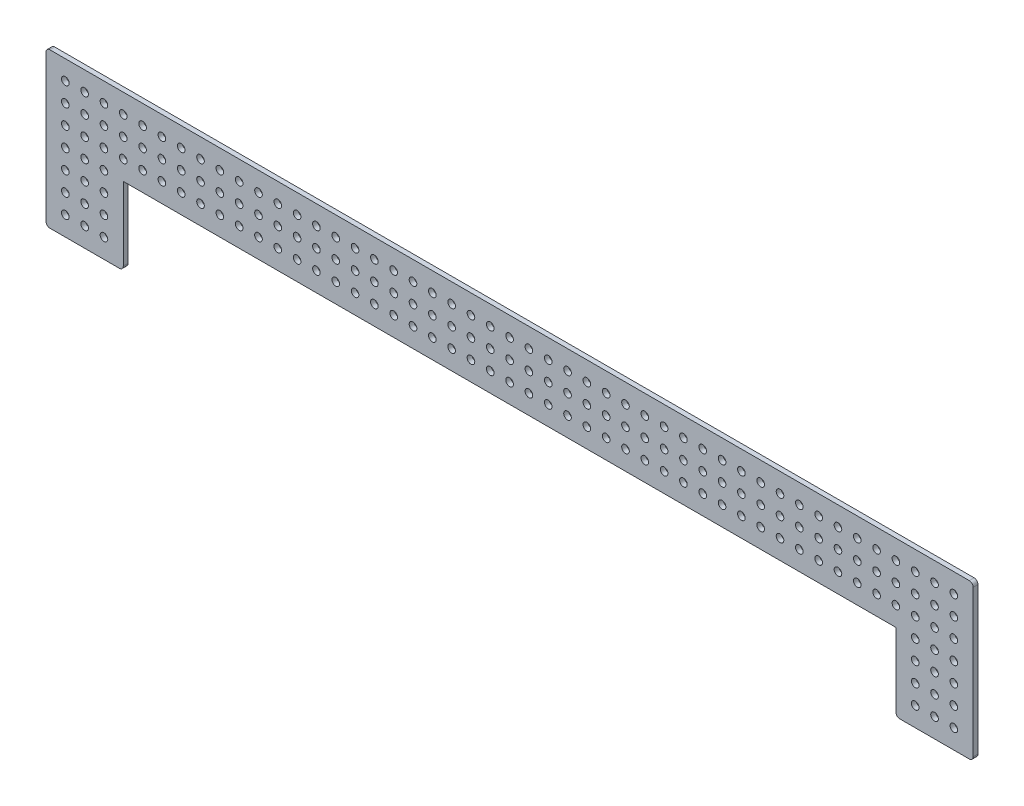
SolidWorks part; units mm, degrees
ref_plane "Front Plane" through (0, 0, 0) normal (0, 0, 1) x (1, 0, 0)
ref_plane "Top Plane" through (0, 0, 0) normal (0, 1, 0) x (1, 0, 0)
ref_plane "Right Plane" through (0, 0, 0) normal (1, 0, 0) x (0, 0, -1)
sketch "Sketch2" plane through (0, 0, 0) normal (0, 0, 1) x (1, 0, 0)
  line L1 (-478.1332, -46.4778) -> (126.3868, -46.4778)
  line L2 (-480.6732, -49.0178) -> (-480.6732, -97.2778)
  line L3 (-480.6732, -97.2778) -> (128.9268, -97.2778)
  line L4 (128.9268, -49.0178) -> (128.9268, -97.2778)
  line L5 (-480.6732, -97.2778) -> (-429.8732, -97.2778)
  line L6 (-480.6732, -97.2778) -> (-480.6732, -145.5378)
  line L7 (-478.1332, -148.0778) -> (-432.4132, -148.0778)
  line L8 (-429.8732, -97.2778) -> (-429.8732, -145.5378)
  line L9 (78.1268, -97.2778) -> (128.9268, -97.2778)
  line L10 (78.1268, -97.2778) -> (78.1268, -145.5378)
  line L11 (80.6668, -148.0778) -> (126.3868, -148.0778)
  line L12 (128.9268, -97.2778) -> (128.9268, -145.5378)
  arc A0 (78.1268, -145.5378) -> (80.6668, -148.0778) centre (80.6668, -145.5378) ccw
  arc A1 (126.3868, -148.0778) -> (128.9268, -145.5378) centre (126.3868, -145.5378) ccw
  arc A2 (126.3868, -46.4778) -> (128.9268, -49.0178) centre (126.3868, -49.0178) cw
  arc A3 (-432.4132, -148.0778) -> (-429.8732, -145.5378) centre (-432.4132, -145.5378) ccw
  arc A4 (-480.6732, -145.5378) -> (-478.1332, -148.0778) centre (-478.1332, -145.5378) ccw
  arc A5 (-478.1332, -46.4778) -> (-480.6732, -49.0178) centre (-478.1332, -49.0178) ccw
  point P12 (0, 0)
  point P13 (0, 0)
  point P16 (78.1268, -148.0778)
  point P19 (128.9268, -148.0778)
  point P22 (128.9268, -46.4778)
  point P25 (-429.8732, -148.0778)
  point P28 (-480.6732, -148.0778)
  dimension "D7" = 2.54
  dimension "D1" = 50.8
  dimension "D2" = 609.6
  dimension "D3" = 50.8
  dimension "D4" = 50.8
  dimension "3" = 50.8
  dimension "D6" = 50.8
extrude "Boss-Extrude1" add sketch "Sketch2" along normal blind 3.175 contours L4 L1 L2 L3 | L8 L3 L6 L7 | L12 L3 L10 L11 region at (-175.8732, -71.88, 0) region at (-455.2732, -122.6511, 0) region at (103.5268, -122.6511, 0)
sketch "Sketch3" plane through (0, 0, 3.175) normal (0, 0, 1) x (1, 0, 0)
  line L0 (-478.1332, -46.4778) -> (126.3868, -46.4778) construction
  line L1 (-480.6732, -49.0178) -> (-480.6732, -145.5378) construction
  line L2 (-478.1332, -148.0778) -> (-432.4132, -148.0778) construction
  line L3 (80.6668, -148.0778) -> (126.3868, -148.0778) construction
  line L4 (78.1268, -97.2778) -> (78.1268, -145.5378) construction
  circle A0 centre (-467.9732, -59.1778) radius 2.505
  circle A1 centre (-455.2732, -59.1778) radius 2.505
  circle A2 centre (-442.5732, -59.1778) radius 2.505
  circle A3 centre (-429.8732, -59.1778) radius 2.505
  circle A4 centre (-417.1732, -59.1778) radius 2.505
  circle A5 centre (-404.4732, -59.1778) radius 2.505
  circle A6 centre (-391.7732, -59.1778) radius 2.505
  circle A7 centre (-379.0732, -59.1778) radius 2.505
  circle A8 centre (-366.3732, -59.1778) radius 2.505
  circle A9 centre (-353.6732, -59.1778) radius 2.505
  circle A10 centre (-340.9732, -59.1778) radius 2.505
  circle A11 centre (-328.2732, -59.1778) radius 2.505
  circle A12 centre (-315.5732, -59.1778) radius 2.505
  circle A13 centre (-302.8732, -59.1778) radius 2.505
  circle A14 centre (-290.1732, -59.1778) radius 2.505
  circle A15 centre (-277.4732, -59.1778) radius 2.505
  circle A16 centre (-264.7732, -59.1778) radius 2.505
  circle A17 centre (-252.0732, -59.1778) radius 2.505
  circle A18 centre (-239.3732, -59.1778) radius 2.505
  circle A19 centre (-226.6732, -59.1778) radius 2.505
  circle A20 centre (-213.9732, -59.1778) radius 2.505
  circle A21 centre (-201.2732, -59.1778) radius 2.505
  circle A22 centre (-188.5732, -59.1778) radius 2.505
  circle A23 centre (-175.8732, -59.1778) radius 2.505
  circle A24 centre (-163.1732, -59.1778) radius 2.505
  circle A25 centre (-150.4732, -59.1778) radius 2.505
  circle A26 centre (-137.7732, -59.1778) radius 2.505
  circle A27 centre (-125.0732, -59.1778) radius 2.505
  circle A28 centre (-112.3732, -59.1778) radius 2.505
  circle A29 centre (-99.6732, -59.1778) radius 2.505
  circle A30 centre (-86.9732, -59.1778) radius 2.505
  circle A31 centre (-74.2732, -59.1778) radius 2.505
  circle A32 centre (-61.5732, -59.1778) radius 2.505
  circle A33 centre (-48.8732, -59.1778) radius 2.505
  circle A34 centre (-36.1732, -59.1778) radius 2.505
  circle A35 centre (-23.4732, -59.1778) radius 2.505
  circle A36 centre (-10.7732, -59.1778) radius 2.505
  circle A37 centre (1.9268, -59.1778) radius 2.505
  circle A38 centre (14.6268, -59.1778) radius 2.505
  circle A39 centre (27.3268, -59.1778) radius 2.505
  circle A40 centre (40.0268, -59.1778) radius 2.505
  circle A41 centre (52.7268, -59.1778) radius 2.505
  circle A42 centre (65.4268, -59.1778) radius 2.505
  circle A43 centre (78.1268, -59.1778) radius 2.505
  circle A44 centre (90.8268, -59.1778) radius 2.505
  circle A45 centre (103.5268, -59.1778) radius 2.505
  circle A46 centre (116.2268, -59.1778) radius 2.505
  circle A47 centre (-455.2732, -71.8778) radius 2.505
  circle A48 centre (-442.5732, -71.8778) radius 2.505
  circle A49 centre (-429.8732, -71.8778) radius 2.505
  circle A50 centre (-417.1732, -71.8778) radius 2.505
  circle A51 centre (-404.4732, -71.8778) radius 2.505
  circle A52 centre (-391.7732, -71.8778) radius 2.505
  circle A53 centre (-379.0732, -71.8778) radius 2.505
  circle A54 centre (-366.3732, -71.8778) radius 2.505
  circle A55 centre (-353.6732, -71.8778) radius 2.505
  circle A56 centre (-340.9732, -71.8778) radius 2.505
  circle A57 centre (-328.2732, -71.8778) radius 2.505
  circle A58 centre (-315.5732, -71.8778) radius 2.505
  circle A59 centre (-302.8732, -71.8778) radius 2.505
  circle A60 centre (-290.1732, -71.8778) radius 2.505
  circle A61 centre (-277.4732, -71.8778) radius 2.505
  circle A62 centre (-264.7732, -71.8778) radius 2.505
  circle A63 centre (-252.0732, -71.8778) radius 2.505
  circle A64 centre (-239.3732, -71.8778) radius 2.505
  circle A65 centre (-226.6732, -71.8778) radius 2.505
  circle A66 centre (-213.9732, -71.8778) radius 2.505
  circle A67 centre (-201.2732, -71.8778) radius 2.505
  circle A68 centre (-188.5732, -71.8778) radius 2.505
  circle A69 centre (-175.8732, -71.8778) radius 2.505
  circle A70 centre (-163.1732, -71.8778) radius 2.505
  circle A71 centre (-150.4732, -71.8778) radius 2.505
  circle A72 centre (-137.7732, -71.8778) radius 2.505
  circle A73 centre (-125.0732, -71.8778) radius 2.505
  circle A74 centre (-112.3732, -71.8778) radius 2.505
  circle A75 centre (-99.6732, -71.8778) radius 2.505
  circle A76 centre (-86.9732, -71.8778) radius 2.505
  circle A77 centre (-74.2732, -71.8778) radius 2.505
  circle A78 centre (-61.5732, -71.8778) radius 2.505
  circle A79 centre (-48.8732, -71.8778) radius 2.505
  circle A80 centre (-36.1732, -71.8778) radius 2.505
  circle A81 centre (-23.4732, -71.8778) radius 2.505
  circle A82 centre (-10.7732, -71.8778) radius 2.505
  circle A83 centre (1.9268, -71.8778) radius 2.505
  circle A84 centre (14.6268, -71.8778) radius 2.505
  circle A85 centre (27.3268, -71.8778) radius 2.505
  circle A86 centre (40.0268, -71.8778) radius 2.505
  circle A87 centre (52.7268, -71.8778) radius 2.505
  circle A88 centre (65.4268, -71.8778) radius 2.505
  circle A89 centre (78.1268, -71.8778) radius 2.505
  circle A90 centre (90.8268, -71.8778) radius 2.505
  circle A91 centre (103.5268, -71.8778) radius 2.505
  circle A92 centre (116.2268, -71.8778) radius 2.505
  circle A93 centre (-455.2732, -84.5778) radius 2.505
  circle A94 centre (-442.5732, -84.5778) radius 2.505
  circle A95 centre (-429.8732, -84.5778) radius 2.505
  circle A96 centre (-417.1732, -84.5778) radius 2.505
  circle A97 centre (-404.4732, -84.5778) radius 2.505
  circle A98 centre (-391.7732, -84.5778) radius 2.505
  circle A99 centre (-379.0732, -84.5778) radius 2.505
  circle A100 centre (-366.3732, -84.5778) radius 2.505
  circle A101 centre (-353.6732, -84.5778) radius 2.505
  circle A102 centre (-340.9732, -84.5778) radius 2.505
  circle A103 centre (-328.2732, -84.5778) radius 2.505
  circle A104 centre (-315.5732, -84.5778) radius 2.505
  circle A105 centre (-302.8732, -84.5778) radius 2.505
  circle A106 centre (-290.1732, -84.5778) radius 2.505
  circle A107 centre (-277.4732, -84.5778) radius 2.505
  circle A108 centre (-264.7732, -84.5778) radius 2.505
  circle A109 centre (-252.0732, -84.5778) radius 2.505
  circle A110 centre (-239.3732, -84.5778) radius 2.505
  circle A111 centre (-226.6732, -84.5778) radius 2.505
  circle A112 centre (-213.9732, -84.5778) radius 2.505
  circle A113 centre (-201.2732, -84.5778) radius 2.505
  circle A114 centre (-188.5732, -84.5778) radius 2.505
  circle A115 centre (-175.8732, -84.5778) radius 2.505
  circle A116 centre (-163.1732, -84.5778) radius 2.505
  circle A117 centre (-150.4732, -84.5778) radius 2.505
  circle A118 centre (-137.7732, -84.5778) radius 2.505
  circle A119 centre (-125.0732, -84.5778) radius 2.505
  circle A120 centre (-112.3732, -84.5778) radius 2.505
  circle A121 centre (-99.6732, -84.5778) radius 2.505
  circle A122 centre (-86.9732, -84.5778) radius 2.505
  circle A123 centre (-74.2732, -84.5778) radius 2.505
  circle A124 centre (-61.5732, -84.5778) radius 2.505
  circle A125 centre (-48.8732, -84.5778) radius 2.505
  circle A126 centre (-36.1732, -84.5778) radius 2.505
  circle A127 centre (-23.4732, -84.5778) radius 2.505
  circle A128 centre (-10.7732, -84.5778) radius 2.505
  circle A129 centre (1.9268, -84.5778) radius 2.505
  circle A130 centre (14.6268, -84.5778) radius 2.505
  circle A131 centre (27.3268, -84.5778) radius 2.505
  circle A132 centre (40.0268, -84.5778) radius 2.505
  circle A133 centre (52.7268, -84.5778) radius 2.505
  circle A134 centre (65.4268, -84.5778) radius 2.505
  circle A135 centre (78.1268, -84.5778) radius 2.505
  circle A136 centre (90.8268, -84.5778) radius 2.505
  circle A137 centre (103.5268, -84.5778) radius 2.505
  circle A138 centre (116.2268, -84.5778) radius 2.505
  circle A139 centre (-467.9732, -71.8778) radius 2.505
  circle A140 centre (-467.9732, -84.5778) radius 2.505
  circle A141 centre (-467.9732, -135.3778) radius 2.505
  circle A142 centre (-455.2732, -135.3778) radius 2.505
  circle A143 centre (-442.5732, -135.3778) radius 2.505
  circle A144 centre (-455.2732, -122.6778) radius 2.505
  circle A145 centre (-442.5732, -122.6778) radius 2.505
  circle A146 centre (-455.2732, -109.9778) radius 2.505
  circle A147 centre (-442.5732, -109.9778) radius 2.505
  circle A148 centre (-455.2732, -97.2778) radius 2.505
  circle A149 centre (-442.5732, -97.2778) radius 2.505
  circle A150 centre (-455.2732, -84.5778) radius 2.505
  circle A151 centre (-442.5732, -84.5778) radius 2.505
  circle A152 centre (-455.2732, -71.8778) radius 2.505
  circle A153 centre (-442.5732, -71.8778) radius 2.505
  circle A154 centre (-467.9732, -122.6778) radius 2.505
  circle A155 centre (-467.9732, -109.9778) radius 2.505
  circle A156 centre (-467.9732, -97.2778) radius 2.505
  circle A157 centre (-467.9732, -84.5778) radius 2.505
  circle A158 centre (-467.9732, -71.8778) radius 2.505
  circle A159 centre (90.8268, -135.3778) radius 2.505
  circle A160 centre (103.5268, -135.3778) radius 2.505
  circle A161 centre (116.2268, -135.3778) radius 2.505
  circle A162 centre (103.5268, -122.6778) radius 2.505
  circle A163 centre (116.2268, -122.6778) radius 2.505
  circle A164 centre (103.5268, -109.9778) radius 2.505
  circle A165 centre (116.2268, -109.9778) radius 2.505
  circle A166 centre (103.5268, -97.2778) radius 2.505
  circle A167 centre (116.2268, -97.2778) radius 2.505
  circle A168 centre (103.5268, -84.5778) radius 2.505
  circle A169 centre (116.2268, -84.5778) radius 2.505
  circle A170 centre (103.5268, -71.8778) radius 2.505
  circle A171 centre (116.2268, -71.8778) radius 2.505
  circle A172 centre (90.8268, -122.6778) radius 2.505
  circle A173 centre (90.8268, -109.9778) radius 2.505
  circle A174 centre (90.8268, -97.2778) radius 2.505
  circle A175 centre (90.8268, -84.5778) radius 2.505
  circle A176 centre (90.8268, -71.8778) radius 2.505
  dimension "5.01mm" = 5.01
  dimension "D6" = 5.01
  dimension "D11" = 5.01
  dimension "D2" = 12.7
  dimension "D3" = 12.7
  dimension "D7" = 12.7
  dimension "D8" = 12.7
  dimension "D12" = 12.7
  dimension "D13" = 12.7
  dimension "D4" = 47
  dimension "D5" = 3
  dimension "D9" = 3
  dimension "D10" = 6
  dimension "D14" = 3
  dimension "D15" = 6
extrude "Cut-Extrude1" cut sketch "Sketch3" against normal through all
